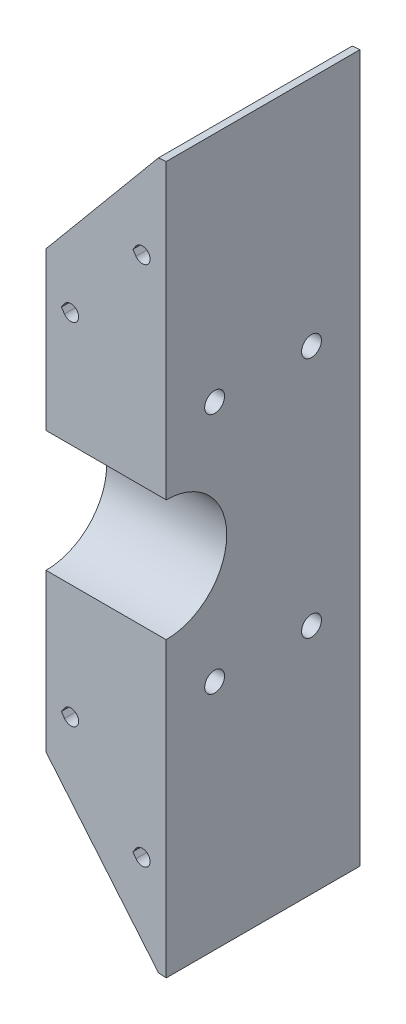
SolidWorks part; units mm, degrees
ref_plane "Front Plane" through (0, 0, 0) normal (1, 0, 0) x (0, 1, 0)
ref_plane "Top Plane" through (0, 0, 0) normal (0, 0, 1) x (0, 1, 0)
ref_plane "Right Plane" through (0, 0, 0) normal (0, 1, 0) x (-1, 0, 0)
sketch "Sketch1" plane through (0, 0, 0) normal (0, 0, 1) x (0, 1, 0)
  line L0 (-75, 0) -> (75, 0) construction
  line L1 (-75, 0) -> (-74.76, 0.2) construction
  line L2 (75, 0) -> (74.76, 0.2) construction
  line L3 (-45, 25) -> (45, 25)
  line L4 (-60, 0) -> (-30, 25) construction
  line L5 (30, 25) -> (60, 0) construction
  line L6 (-53.8542, 5.1215) -> (-53.8542, 7.0747) construction
  line L7 (-36.1458, 19.8785) -> (-36.1458, 21.8318) construction
  line L8 (-54.772, 6.4321) -> (-53.8542, 7.0747)
  line L9 (-52.9365, 6.4321) -> (-53.8542, 7.0747)
  line L10 (-37.0635, 21.1892) -> (-36.1458, 21.8318)
  line L11 (-35.228, 21.1892) -> (-36.1458, 21.8318)
  line L12 (36.1458, 19.8785) -> (36.1458, 21.8318) construction
  line L13 (35.228, 21.1892) -> (36.1458, 21.8318)
  line L14 (37.0635, 21.1892) -> (36.1458, 21.8318)
  line L15 (53.8542, 5.1215) -> (53.8542, 7.0747) construction
  line L16 (52.9365, 6.4321) -> (53.8542, 7.0747)
  line L17 (54.772, 6.4321) -> (53.8542, 7.0747)
  line L18 (-74.76, 0.2) -> (74.76, 0.2)
  line L19 (-74.76, 0.2) -> (-45, 25)
  line L20 (74.76, 0.2) -> (45, 25)
  arc A0 (-54.772, 6.4321) -> (-52.9365, 6.4321) centre (-53.8542, 5.1215) ccw
  arc A1 (-37.0635, 21.1892) -> (-35.228, 21.1892) centre (-36.1458, 19.8785) ccw
  arc A2 (35.228, 21.1892) -> (37.0635, 21.1892) centre (36.1458, 19.8785) ccw
  arc A3 (52.9365, 6.4321) -> (54.772, 6.4321) centre (53.8542, 5.1215) ccw
  point P5 (0, 0)
  point P22 (73.5085, 1.4915)
  point P27 (-73.8738, 0.7383)
  point P28 (77.5013, 1.7433)
  point P31 (0, 0)
  point P32 (-61.5831, 25)
  point P33 (73.6231, 1.3769)
  point P34 (0, 25)
  dimension "D8" = 3.2
  dimension "D9" = 3.2
  dimension "D15" = 1.6
  dimension "D16" = 1.6
  dimension "D2" = 25
  dimension "D3" = 150
  dimension "D4" = 15
  dimension "D5" = 15
  dimension "D6" = 8
  dimension "D10" = 55
  dimension "D11" = 55
  dimension "D12" = 55
  dimension "D13" = 55
  dimension "D7" = 8
  dimension "D14" = 8
  dimension "D17" = 8
  dimension "D18" = 0.2
  dimension "D19" = 90
extrude "Boss-Extrude1" add sketch "Sketch1" against normal blind 40
sketch "Sketch2" plane through (-25, 0, 0) normal (-1, 0, 0) x (0, -1, 0)
  line L0 (-25, -10) -> (-25, -30) construction
  line L1 (-45, -40) -> (-45, 0) construction
  line L4 (25, -10) -> (25, -30) construction
  line L5 (45, -40) -> (45, 0) construction
  line L6 (-45, -20) -> (45, -20) construction
  line L7 (-45, 0) -> (45, 0) construction
  line L8 (-12.5, 0) -> (12.5, 0)
  circle A0 centre (-25, -10) radius 4
  circle A1 centre (-25, -30) radius 4
  circle A2 centre (-25, -30) radius 2.05
  circle A3 centre (-25, -10) radius 2.05
  circle A4 centre (25, -10) radius 4
  circle A5 centre (25, -10) radius 2.05
  circle A6 centre (25, -30) radius 4
  circle A7 centre (25, -30) radius 2.05
  arc A8 (-12.5, 0) -> (12.5, 0) centre (0, 0) ccw
  point P10 (-25, -20)
  point P11 (25, -20)
  line M4 (45, 0) -> (-45, 0)
  dimension "D6" = 8
  dimension "D5" = 8
  dimension "D7" = 4.1
  dimension "D8" = 4.1
  dimension "D9" = 8
  dimension "D10" = 4.1
  dimension "D11" = 8
  dimension "D12" = 4.1
  dimension "D13" = 12.5
  dimension "D1" = 20
  dimension "D2" = 20
  dimension "D3" = 20
  dimension "D4" = 20
extrude "Cut-Extrude1" cut sketch "Sketch2" against normal through all contours A3 | A2 | A7 | A5 | A8 M4 region at (-25, 0, -5.3052) region at (-25, 25, -30) region at (-25, 25, -10) region at (-25, -25, -10) region at (-25, -25, -30)
extrude "Cut-Extrude2" cut sketch "Sketch2<4>" against normal blind 6
sketch "Sketch2<4>" plane through (-25, 0, 0) normal (-1, 0, 0) x (0, -1, 0) same geometry as "Sketch2"
chamfer "Chamfer1" distance 2.5 angle 45 2 edges at (-0.2, -74.76, -20) (-0.2, 74.76, -20) first distance on face at (-12.6, -59.88, -20) first distance on face at (-12.6, 59.88, -20)
sketch "Sketch3" plane through (0, 0, -40) normal (0, 0, -1) x (1, 0, 0)
  line L1 (-22.6285, 38.8958) -> (-17.1285, 38.8958)
  line L2 (-22.6285, 38.8958) -> (-22.6285, 33.3958)
  line L3 (-22.6285, 33.3958) -> (-17.1285, 33.3958)
  line L4 (-17.1285, 38.8958) -> (-17.1285, 33.3958)
  line L5 (-22.6285, 38.8958) -> (-17.1285, 33.3958) construction
  line L6 (-22.6285, 33.3958) -> (-17.1285, 38.8958) construction
  line L7 (-7.8715, 56.6042) -> (-2.3715, 56.6042)
  line L8 (-7.8715, 56.6042) -> (-7.8715, 51.1042)
  line L9 (-7.8715, 51.1042) -> (-2.3715, 51.1042)
  line L10 (-2.3715, 56.6042) -> (-2.3715, 51.1042)
  line L11 (-7.8715, 56.6042) -> (-2.3715, 51.1042) construction
  line L12 (-7.8715, 51.1042) -> (-2.3715, 56.6042) construction
  line L13 (-22.6285, -33.3958) -> (-17.1285, -33.3958)
  line L14 (-22.6285, -33.3958) -> (-22.6285, -38.8958)
  line L15 (-22.6285, -38.8958) -> (-17.1285, -38.8958)
  line L16 (-17.1285, -33.3958) -> (-17.1285, -38.8958)
  line L17 (-22.6285, -33.3958) -> (-17.1285, -38.8958) construction
  line L18 (-22.6285, -38.8958) -> (-17.1285, -33.3958) construction
  line L19 (-7.8715, -51.1042) -> (-2.3715, -51.1042)
  line L20 (-7.8715, -51.1042) -> (-7.8715, -56.6042)
  line L21 (-7.8715, -56.6042) -> (-2.3715, -56.6042)
  line L22 (-2.3715, -51.1042) -> (-2.3715, -56.6042)
  line L23 (-7.8715, -51.1042) -> (-2.3715, -56.6042) construction
  line L24 (-7.8715, -56.6042) -> (-2.3715, -51.1042) construction
  point P0 (-19.8785, 36.1458)
  point P6 (-5.1215, 53.8542)
  point P12 (-19.8785, -36.1458)
  point P18 (-5.1215, -53.8542)
  dimension "D1" = 5.5
  dimension "D2" = 5.5
  dimension "D3" = 5.5
  dimension "D4" = 5.5
extrude "Cut-Extrude3" cut sketch "Sketch3" against normal blind 5
equation "\"D5@Sketch1\"=\"D4@Sketch1\""
equation "\"D4@Sketch2\"=\"D3@Sketch2\""
equation "\"D2@Sketch3\"=\"D1@Sketch3\""
equation "\"D3@Sketch3\"=\"D1@Sketch3\""
equation "\"D4@Sketch3\"=\"D1@Sketch3\""
